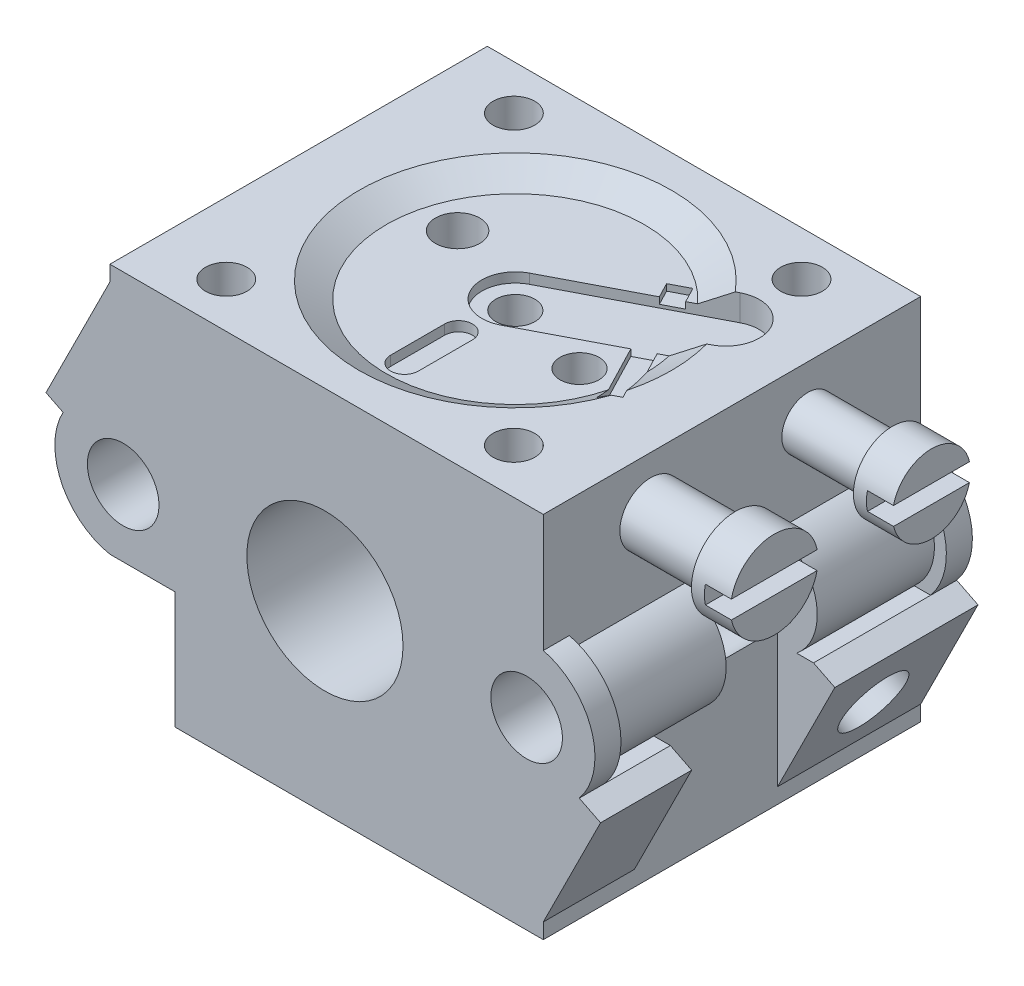
SolidWorks part; units mm, degrees
ref_plane "Front Plane" through (0, 0, 0) normal (0, 0, 1) x (1, 0, 0)
ref_plane "Top Plane" through (0, 0, 0) normal (0, 1, 0) x (1, 0, 0)
ref_plane "Right Plane" through (0, 0, 0) normal (1, 0, 0) x (0, 0, -1)
sketch "Sketch1" plane through (0, 0, 0) normal (0, 0, 1) x (1, 0, 0)
  line L0 (-16.5216, 14.1483) -> (16.7784, 14.1483)
  line L1 (16.7784, 14.1483) -> (16.7784, 5.0898)
  line L2 (-16.5216, -14.1517) -> (16.7784, -14.1517)
  line L3 (16.7784, -14.1517) -> (16.7784, -12.9706)
  line L4 (16.7784, -12.9706) -> (21.1796, -4.1683)
  line L5 (21.1796, -4.1683) -> (19.5423, -3.3496)
  line L6 (-16.5216, -14.1517) -> (-16.5216, -5.1517)
  line L7 (-16.5216, 14.1483) -> (-16.5216, 12.9671)
  line L8 (-16.5216, 12.9671) -> (-21.4312, 3.1478)
  line L9 (-21.4312, 3.1478) -> (-20.1213, 2.4928)
  line L10 (-0.0018, -0.0017) -> (-15.5018, -0.0017) construction
  line L11 (-0.0018, -0.0017) -> (-0.0018, 4.1303) construction
  line L12 (-0.0018, -8.5017) -> (-0.0018, -14.1517) construction
  line L13 (-6.7084, 14.1483) -> (-6.7084, -14.1517) construction
  circle A0 centre (0, 0) radius 6
  circle A1 centre (-15.5018, -0.0017) radius 2.75
  circle A2 centre (15.4982, -0.0017) radius 2.75
  arc A4 (-20.1213, 2.4928) -> (-16.5216, -5.1517) centre (-15.5018, -0.0017) ccw
  arc A5 (19.5423, -3.3496) -> (16.7784, 5.0898) centre (15.4982, -0.0017) ccw
  point P24 (-6.7084, -0.0017)
  dimension "D2" = 12
  dimension "D4" = 5.5
  dimension "D5" = 2.5
  dimension "D6" = 2.5
  dimension "D8" = 33.3
  dimension "D3" = 28.3
  dimension "D7" = 9
extrude "Boss-Extrude1" add sketch "Sketch1" along normal blind 29
sketch "Sketch2" plane through (0, -14.1517, 0) normal (0, -1, 0) x (1, 0, 0)
  line L0 (-16.5216, 0) -> (16.7784, 0) construction
  line L1 (-16.5216, 29) -> (-16.5216, 0) construction
  line L2 (-16.5216, 29) -> (16.7784, 29) construction
  line L3 (16.7784, 29) -> (16.7784, 0) construction
  circle A0 centre (-14.0216, 2.5) radius 1.15
  circle A1 centre (14.2784, 26.5) radius 1.15
  dimension "D1" = 2.5
  dimension "D3" = 2.5
  dimension "D5" = 2.3
  dimension "D6" = 2.3
  dimension "D2" = 2.5
  dimension "D4" = 2.5
extrude "Cut-Extrude1" cut sketch "Sketch2" against normal blind 3.3
sketch "Sketch3" plane through (0, -14.1517, 0) normal (0, -1, 0) x (1, 0, 0)
  line L0 (14.7784, 19.9154) -> (14.7784, 3.0392)
  line L1 (13.7784, 2.0392) -> (8.8036, 2.0392)
  line L2 (7.8036, 3.0392) -> (7.8036, 3.5344)
  line L3 (7.2178, 4.9486) -> (4.8538, 7.3126)
  line L4 (4.2681, 8.7268) -> (4.2681, 16.8984)
  line L5 (5.2681, 17.8984) -> (9.0486, 17.8984)
  line L6 (10.3227, 18.3567) -> (13.1414, 20.6862)
  line L7 (16.7784, 29) -> (16.7784, 0) construction
  arc A0 (4.2681, 16.8984) -> (5.2681, 17.8984) centre (5.2681, 16.8984) cw
  arc A1 (8.8036, 2.0392) -> (7.8036, 3.0392) centre (8.8036, 3.0392) cw
  arc A2 (14.7784, 3.0392) -> (13.7784, 2.0392) centre (13.7784, 3.0392) cw
  arc A3 (14.7784, 19.9154) -> (13.1414, 20.6862) centre (13.7784, 19.9154) ccw
  arc A4 (9.0486, 17.8984) -> (10.3227, 18.3567) centre (9.0486, 19.8984) ccw
  arc A5 (4.8538, 7.3126) -> (4.2681, 8.7268) centre (6.2681, 8.7268) cw
  arc A6 (7.8036, 3.5344) -> (7.2178, 4.9486) centre (5.8036, 3.5344) ccw
  point P11 (4.2681, 17.8984)
  point P16 (14.7784, 2.0392)
  point P19 (14.7784, 22.0392)
  point P22 (9.7681, 17.8984)
  point P25 (4.2681, 7.8984)
  point P28 (7.8036, 4.3628)
  dimension "D7" = 1
  dimension "D8" = 2
  dimension "D1" = 20
  dimension "D2" = 2
  dimension "D3" = 6.5
  dimension "D4" = 5.5
  dimension "D5" = 10
  dimension "D6" = 5
extrude "Cut-Extrude2" cut sketch "Sketch3" against normal blind 1.2
sketch "Sketch4" plane through (0, -12.9517, 0) normal (0, -1, 0) x (1, 0, 0)
  line L0 (4.2681, 11.7241) -> (5.7681, 11.7241) construction
  line L1 (4.2681, 16.8984) -> (4.2681, 8.7268) construction
  circle A0 centre (9.5181, 11.7241) radius 3.75
  dimension "D1" = 7.5
extrude "Cut-Extrude3" cut sketch "Sketch4" against normal blind 5.5
fillet "Fillet1" radius 0.4 15 edges at (9.7256, -12.9517, 18.0164) (11.732, -12.9517, 19.5215) (14.2044, -12.9517, 20.8201) (14.7784, -12.9517, 11.4773) (14.4855, -12.9517, 2.3321) (11.291, -12.9517, 2.0392) (8.0965, -12.9517, 2.3321) (7.8036, -12.9517, 3.2868) (7.6514, -12.9517, 4.2998) (6.0358, -12.9517, 6.1306) (4.4203, -12.9517, 7.9614) (4.2681, -12.9517, 12.8126) (4.561, -12.9517, 17.6055) (9.5181, -12.9517, 7.9741) (7.1583, -12.9517, 17.8984)
sketch "Sketch5" plane through (0, -14.1517, 0) normal (0, -1, 0) x (1, 0, 0)
  line L0 (-16.5216, 29) -> (-16.5216, 0) construction
  line L1 (-16.5216, 29) -> (-16.5216, 0) construction
  line L2 (-11.5216, 27.6514) -> (-11.5216, 29.7011)
  line L3 (-11.5216, 29.7011) -> (-18.1114, 29.7011)
  line L4 (-18.1114, 29.7011) -> (-18.1114, 11.7988)
  line L5 (-18.1114, 11.7988) -> (-16.5216, 11.7988)
  spline S0 degree 3 poles (-16.5216, 11.7988) (-16.5216, 15.2959) (-16.995, 21.518) (-13.386, 26.4524) (-11.5216, 27.6514) knots 0 0 0 0 0.621929 1 1 1 1
  dimension "D1" = 5
extrude "Cut-Extrude4" cut sketch "Sketch5" against normal up to vertex (9 mm away) up to point (-16.5216, -5.1517, 29)
sketch "Sketch6" plane through (0, -14.1517, 0) normal (0, -1, 0) x (1, 0, 0)
  line L3 (-14.0216, 16.8542) -> (-14.0216, 0)
  line L4 (-14.0216, 16.8542) -> (-14.0216, 6.15)
  line L5 (-4.6774, 2.5) -> (-4.6774, 6.15)
  line L6 (-16.5216, 2.5) -> (16.7784, 2.5)
  line L7 (-10.3716, 2.5) -> (-4.6774, 2.5)
  line L8 (-4.6774, 6.15) -> (-2.3104, 9.313)
  line L9 (-1.478, 17.6912) -> (-1.478, 24.4414)
  line L10 (-10.1693, 25.5486) -> (-8.69, 26.5)
  line L11 (-8.69, 26.5) -> (-4.0102, 26.5)
  line L12 (-11.5216, 29) -> (16.7784, 29) construction
  arc A1 (-1.478, 17.6912) -> (-2.3104, 9.313) centre (-0.312, 13.3449) ccw
  circle A2 centre (-14.0216, 2.5) radius 3.65
  arc A3 (-10.3716, 2.5) -> (-14.0216, 6.15) centre (-14.0216, 2.5) ccw
  arc A4 (-4.0102, 26.5) -> (-1.478, 24.4414) centre (-1.478, 27.028) ccw
  spline S5 degree 3 poles (-855.3284, -2844.1249) (189.1992, -110.999) (10.5569, 51.8456) (-12.3332, 23.4176) (-12.7457, 22.7203) (-13.2189, 21.6091) (-13.3521, 21.2287) (-13.5797, 20.4319) (-13.6735, 20.0175) (-20.9923, -21.1961) (131.6818, -196.7104) (-2455.4259, 1757.4527) knots -11.208202 -11.208202 -11.208202 -11.208202 0.25 0.25 0.5 0.5 0.625 0.625 0.75 0.75 12.624627 12.624627 12.624627 12.624627 only from (-10.1693, 25.5486) to (-14.0216, 16.8542)
  spline S6 degree 3 poles (-10.1693, 25.5486) (-10.7925, 25.1479) (-11.3557, 24.6316) (-12.3332, 23.4176) (-12.7457, 22.7203) (-13.2189, 21.6091) (-13.3521, 21.2287) (-13.5797, 20.4319) (-13.6735, 20.0175) (-13.9022, 18.7295) (-13.9838, 17.8111) (-14.0216, 16.8542) knots 0 0 0 0 0.25 0.25 0.5 0.5 0.625 0.625 0.75 0.75 1 1 1 1
  dimension "D4" = 4.5
  dimension "D5" = 2.5
  dimension "D1" = 2.5
  dimension "D2" = 2.5
  dimension "D3" = 2.5
extrude "Cut-Extrude5" cut sketch "Sketch6" against normal blind 2
fillet "Fillet2" radius 2 10 edges at (-11.4406, -12.1517, 5.0809) (-7.5245, -12.1517, 2.5) (-4.6774, -12.1517, 4.325) (-3.4939, -12.1517, 7.7315) (-4.7899, -12.1517, 13.7898) (-1.478, -12.1517, 21.0663) (-3.1097, -12.1517, 25.021) (-6.3501, -12.1517, 26.5) first distance on face at (-11.8186, -13.1517, 4.703) first distance on face at (-7.5245, -13.1517, 2.5) first distance on face at (-4.6774, -13.1517, 4.325) first distance on face at (-3.4939, -13.1517, 7.7315) first distance on face at (-3.3421, -13.1517, 13.6459) first distance on face at (-1.478, -13.1517, 21.0663) first distance on face at (-2.9269, -13.1517, 25.2458) first distance on face at (-6.3501, -13.1517, 26.5) first distance on face at (-11.1324, -12.6517, 23.375) first distance on face at (-9.0598, -12.9017, 26.2622)
sketch "Sketch7" plane through (0, -12.1517, 0) normal (0, -1, 0) x (1, 0, 0)
  line L0 (-1.478, 17.6911) -> (-1.478, 24.4414) construction
  line L4 (-1.478, 22.2691) -> (-1.478, 20.0681)
  line L5 (-4.6774, 2.5) -> (-4.6774, 6.15) construction
  line L7 (-8.067, 4.8823) -> (-8.067, 4.1775)
  line L9 (-4.6774, 5.5811) -> (-4.6774, 3.4787)
  line L10 (-4.6774, 5.5811) -> (-8.067, 4.8823)
  line L11 (-4.6774, 3.4787) -> (-8.067, 4.1775)
  line L12 (-8.067, 4.5299) -> (-4.6774, 4.5299) construction
  line L13 (-1.478, 22.2691) -> (-4.3852, 21.4568)
  line L14 (-4.3852, 21.4568) -> (-4.3852, 20.8805)
  line L15 (-4.3852, 20.8805) -> (-1.478, 20.0681)
  line L16 (-4.3852, 21.1686) -> (-1.478, 21.1686) construction
extrude "Cut-Extrude6" cut sketch "Sketch7" along normal blind 2
sketch "Sketch8" plane through (-1.478, 0, 0) normal (-1, 0, 0) x (0, 0, 1)
  line L0 (20.0681, -14.1517) -> (22.2691, -12.1517) construction
  line L1 (5.7018, -13.6786) -> (3.4204, -12.6249) construction
  circle A0 centre (4.5611, -13.1517) radius 0.6
  circle A1 centre (21.1686, -13.1517) radius 0.6
  dimension "D1" = 1.2
  dimension "D2" = 1.2
extrude "Cut-Extrude7" cut sketch "Sketch8" against normal blind 2 and the other way blind 6
sketch "Sketch9" plane through (0, -14.1517, 0) normal (0, -1, 0) x (1, 0, 0)
  line L0 (-1.478, 17.6911) -> (-4.7523, 14.075) construction
  line L1 (-2.3104, 9.313) -> (-4.7523, 14.075) construction
  line L2 (-3.5314, 11.694) -> (-0.3121, 13.3449) construction
  line L3 (-3.1152, 15.883) -> (-0.3121, 13.3449) construction
  circle A0 centre (-0.3121, 13.3449) radius 1.75
  spline S0 degree 3 poles (-2.3104, 9.313) (-2.5949, 9.4541) (-2.8644, 9.6252) (-3.5035, 10.1334) (-3.8419, 10.5095) (-4.3773, 11.3517) (-4.5742, 11.8176) (-4.8053, 12.7885) (-4.8393, 13.2932) (-4.7406, 14.2863) (-4.608, 14.7745) (-4.1904, 15.6809) (-3.9056, 16.099) (-3.215, 16.8193) (-2.8092, 17.1215) (-2.0827, 17.4941) (-1.7847, 17.6088) (-1.478, 17.6911) knots 0.46016 0.46016 0.46016 0.46016 0.671853 0.671853 1.004508 1.004508 1.337163 1.337163 1.669818 1.669818 2.002473 2.002473 2.335128 2.335128 2.667783 2.667783 2.879476 2.879476 2.879476 2.879476 weights 1 1 1 1 1 1 1 1 1 1 1 1 1 1 1 1 1 1 construction
extrude "Cut-Extrude8" cut sketch "Sketch9" against normal blind 8
sketch "Sketch10" plane through (0, -14.1517, 0) normal (0, -1, 0) x (1, 0, 0)
  circle A0 centre (1.1718, 4.497) radius 1.15
  circle A1 centre (1.1718, 8.1434) radius 1.15
  circle A2 centre (1.1718, 21.1411) radius 1.15
  circle A3 centre (-1.6862, 26.7368) radius 1.15
  circle A4 centre (6.1122, 22.6384) radius 1.15
  dimension "D1" = 2.3
  dimension "D2" = 2.3
  dimension "D3" = 2.3
  dimension "D4" = 2.3
  dimension "D5" = 2.3
extrude "Cut-Extrude9" cut sketch "Sketch10" against normal blind 6
sketch "Sketch12" plane through (16.7784, 0, 0) normal (1, 0, 0) x (0, 0, -1)
  line L0 (-29, -3.3496) -> (-22, -3.3496) construction
  line L1 (-29, -3.3496) -> (0, -3.3496) construction
  line L2 (0, -3.3496) -> (-11, -3.3496) construction
  line L3 (-29, 5.0898) -> (0, 5.0898) construction
  line L5 (-11, -3.3496) -> (-11, 5.0898)
  line L6 (-11, 5.0898) -> (-18, 5.0898)
  line L7 (-18, -3.3496) -> (-18, 5.0898)
  line L8 (-29, -12.9706) -> (0, -12.9706) construction
  line L9 (-22, -3.3496) -> (-18, -3.3496)
  line L10 (-22, -3.3496) -> (-22, -12.9706)
  line L11 (-22, -12.9706) -> (-11, -12.9706)
  line L12 (-11, -3.3496) -> (-11, -12.9706)
  dimension "D1" = 7
  dimension "D2" = 11
  dimension "D3" = 7
extrude "Cut-Extrude10" cut sketch "Sketch12" along normal blind 16
sketch "Sketch13" plane through (0, 0, 11) normal (0, 0, 1) x (1, 0, 0)
  line L0 (19.5423, -3.3496) -> (16.7784, -3.3496) construction
  line L2 (16.7784, 5.0898) -> (16.7784, 2.4321) construction
  line L3 (19.5423, -3.3496) -> (18.2466, -3.3496)
  line L5 (16.7784, 5.0898) -> (16.7784, 4.1362)
  arc A2 (18.2466, -3.3496) -> (16.7784, 4.1362) centre (15.4982, -0.0017) ccw
  arc A3 (19.5423, -3.3496) -> (16.7784, 5.0898) centre (15.4982, -0.0017) ccw construction
  arc A4 (19.5423, -3.3496) -> (16.7784, 5.0898) centre (15.4982, -0.0017) ccw
extrude "Cut-Extrude11" cut sketch "Sketch13" against normal blind 9 and the other way blind 16
sketch "Sketch14" plane through (16.7784, 0, 0) normal (1, 0, 0) x (0, 0, -1)
  circle A0 centre (-20.7529, 10.1028) radius 2.365
  circle A1 centre (-8.6724, 10.1028) radius 2
  dimension "D1" = 4.73
  dimension "D2" = 4
extrude "Boss-Extrude2" add sketch "Sketch14" along normal blind 6.5
sketch "Sketch15" plane through (23.2784, 0, 0) normal (1, 0, 0) x (0, 0, -1)
  circle A0 centre (-20.7529, 10.1028) radius 3.365
  circle A1 centre (-8.6724, 10.1028) radius 3
  circle A2 centre (-8.6724, 10.1028) radius 2 construction
  circle A3 centre (-20.7529, 10.1028) radius 2.365 construction
  dimension "D1" = 1
  dimension "D2" = 1
extrude "Boss-Extrude3" add sketch "Sketch15" along normal blind 3
sketch "Sketch16" plane through (26.2784, 0, 0) normal (1, 0, 0) x (0, 0, -1)
  line L1 (-25.0917, 10.7833) -> (-16.5843, 10.7833)
  line L2 (-25.0917, 10.7833) -> (-25.0917, 9.3938)
  line L3 (-25.0917, 9.3938) -> (-16.5843, 9.3938)
  line L4 (-16.5843, 10.7833) -> (-16.5843, 9.3938)
  line L5 (-12.6142, 10.7833) -> (-3.9933, 10.7833)
  line L6 (-12.6142, 10.7833) -> (-12.6142, 9.3938)
  line L7 (-12.6142, 9.3938) -> (-3.9933, 9.3938)
  line L8 (-3.9933, 10.7833) -> (-3.9933, 9.3938)
extrude "Cut-Extrude12" cut sketch "Sketch16" against normal blind 2
sketch "Sketch17" plane through (0, 0, 0) normal (0, 0, -1) x (-1, 0, 0)
  circle A0 centre (0, -10.1601) radius 1.25
extrude "Cut-Extrude13" cut sketch "Sketch17" against normal blind 5
sketch "Sketch18" plane through (0, 14.1483, 0) normal (0, 1, 0) x (1, 0, 0)
  line L0 (-16.5216, -14.5) -> (16.7784, -14.5) construction
  line L1 (-16.5216, -29) -> (-16.5216, 0) construction
  line L2 (16.7784, -29) -> (16.7784, 0) construction
  circle A0 centre (0.1284, -14.5) radius 12
extrude "Cut-Extrude14" cut sketch "Sketch18" against normal blind 1.25
sketch "Sketch19" plane through (0, 14.1483, 0) normal (0, 1, 0) x (1, 0, 0)
  line L0 (11.05, -3.4316) -> (11.05, -25.5316) construction
  line L1 (0, -14.4816) -> (0, -12.4816) construction
  line L2 (11.05, -25.5316) -> (-11.05, -25.5316) construction
  line L3 (-12.65, -3.4316) -> (12.65, -3.4316) construction
  line L4 (-11.05, -1.8316) -> (-11.05, -27.1316) construction
  line L9 (0, -14.4816) -> (-11.05, -14.4816) construction
  line L10 (0, -14.4816) -> (0, -3.4316) construction
  line L11 (0, -3.4316) -> (0, -14.4816) construction
  line L12 (0, -14.4816) -> (11.05, -14.4816) construction
  line L13 (11.05, -14.4816) -> (0, -14.4816) construction
  line L14 (0, -14.4816) -> (0, -25.5316) construction
  line L15 (11.05, -25.5316) -> (-11.05, -3.4316) construction
  line L16 (11.05, -3.4316) -> (-11.05, -25.5316) construction
  line L17 (0, -3.4316) -> (0, -3.4651) construction
  circle A1 centre (-11.05, -3.4316) radius 1.6
  circle A2 centre (11.05, -3.4316) radius 1.6
  circle A3 centre (-11.05, -25.5316) radius 1.6
  circle A4 centre (11.05, -25.5316) radius 1.6
extrude "Cut-Extrude15" cut sketch "Sketch19" against normal blind 7.2
chamfer "Chamfer1" distance 1.25 angle 59 1 edges at (-11.8716, 12.8983, 14.5) first distance on face at (-11.8716, 12.8983, 14.5)
sketch "Sketch21" plane through (0, 12.8983, 0) normal (0, 1, 0) x (1, 0, 0)
  line L0 (0.1284, -14.5) -> (10.7782, -8.9698) construction
  line L1 (-1.0565, -12.2182) -> (9.5933, -6.688)
  line L2 (1.3133, -16.7818) -> (11.9631, -11.2517)
  line L3 (0.1284, -23.0149) -> (0.1284, -18.8586) construction
  line L4 (-0.9346, -23.0149) -> (-0.9346, -18.8586)
  line L5 (1.1914, -23.0149) -> (1.1914, -18.8586)
  circle A0 centre (-6.643, -12.1644) radius 1.7
  circle A1 centre (0.1284, -14.5) radius 12 construction
  arc A2 (-1.0565, -12.2182) -> (1.3133, -16.7818) centre (0.1284, -14.5) ccw
  arc A3 (11.9631, -11.2517) -> (9.5933, -6.688) centre (10.7782, -8.9698) ccw
  arc A4 (-0.9346, -23.0149) -> (1.1914, -23.0149) centre (0.1284, -23.0149) ccw
  arc A5 (1.1914, -18.8586) -> (-0.9346, -18.8586) centre (0.1284, -18.8586) ccw
  point P7 (5.4533, -11.7349)
  point P12 (0.1284, -20.9367)
extrude "Cut-Extrude16" cut sketch "Sketch21" against normal blind 0.75 and the other way blind 7.2
sketch "Sketch22" plane through (0, 12.1483, 0) normal (0, 1, 0) x (1, 0, 0)
  circle A0 centre (-6.643, -12.1644) radius 1.7
  circle A1 centre (0.1284, -14.5) radius 1.5
extrude "Cut-Extrude17" cut sketch "Sketch22" against normal blind 3
sketch "Sketch23" plane through (0, 12.8983, 0) normal (0, 1, 0) x (1, 0, 0)
  line L0 (4.9096, -7.6578) -> (10.715, -18.8375)
  line L1 (1.3133, -16.7818) -> (11.9631, -11.2517) construction
  line L2 (4.9096, -7.6578) -> (6.2409, -6.9666)
  line L3 (6.2409, -6.9666) -> (12.0462, -18.1462)
  line L4 (12.0462, -18.1462) -> (10.715, -18.8375)
  dimension "D1" = 1.5
extrude "Cut-Extrude18" cut sketch "Sketch23" along normal blind 3 and the other way blind 0.5
sketch "Sketch24" plane through (0, 12.8983, 0) normal (0, 1, 0) x (1, 0, 0)
  circle A0 centre (7.2154, -16.6541) radius 1.5
  dimension "D1" = 3
extrude "Cut-Extrude19" cut sketch "Sketch24" against normal blind 4
sketch "Sketch25" plane through (-18.4041, 9.202, 0) normal (-0.8944, 0.4472, 0) x (0, 0, 1)
  circle A0 centre (5.6129, 0.3039) radius 2.5
extrude "Cut-Extrude20" cut sketch "Sketch25" against normal blind 54
